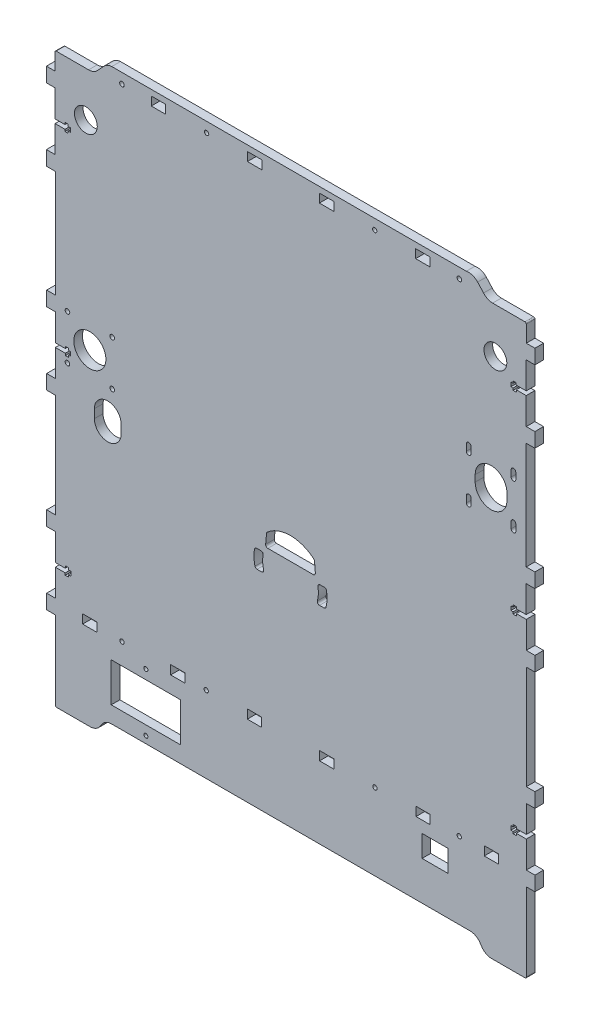
SolidWorks part; units mm, degrees
ref_plane "Спереди" through (0, 0, 0) normal (0, 0, 1) x (1, 0, 0)
ref_plane "Сверху" through (0, 0, 0) normal (0, 1, 0) x (1, 0, 0)
ref_plane "Справа" through (0, 0, 0) normal (1, 0, 0) x (0, 0, -1)
sketch "Эскиз1" plane through (0, 0, 0) normal (0, 0, 1) x (1, 0, 0)
  line L0 (-11.6369, -134.9128) -> (-21.486, -134.9128)
  line L1 (-21.486, -134.9128) -> (-21.486, -128.713)
  line L2 (-11.6369, -128.713) -> (-11.6369, -134.9128)
  line L3 (-21.486, -128.713) -> (-11.6369, -128.713)
  line L4 (-61.6369, -128.7116) -> (-61.6369, -134.9114)
  line L5 (-71.4861, -128.7116) -> (-61.6369, -128.7116)
  line L6 (-71.4861, -134.9114) -> (-71.4861, -128.7116)
  line L7 (-61.6369, -134.9114) -> (-71.4861, -134.9114)
  line L8 (49.4936, -157.9128) -> (49.4936, -142.9128)
  line L9 (49.4936, -142.9128) -> (67.4936, -142.9128)
  line L10 (67.4936, -142.9128) -> (67.4936, -157.9128)
  line L11 (67.4936, -157.9128) -> (49.4936, -157.9128)
  line L12 (-197.4929, 21.4243) -> (-197.4918, 20.0542)
  line L13 (-204.4021, 24.2766) -> (-204.4021, 42.8766)
  line L14 (-195.2929, 25.6494) -> (-195.2929, 25.6766)
  line L15 (127.5652, 42.8766) -> (127.5652, 52.8766)
  line L16 (-193.7921, 24.2485) -> (-193.792, 24.2757)
  line L17 (-195.292, 24.2757) -> (-195.2929, 25.6494)
  line L18 (-195.2921, 21.4269) -> (-195.2921, 21.4541)
  line L19 (-193.7921, 21.4541) -> (-193.7921, 24.2485)
  line L20 (112.4973, 24.3034) -> (112.4973, 24.2763)
  line L21 (114.6973, 24.3037) -> (114.697, 25.6766)
  line L22 (-195.2921, 20.0542) -> (-195.2921, 21.4269)
  line L23 (110.9994, 21.5032) -> (110.9994, 21.4761)
  line L24 (110.9973, 24.2752) -> (110.9994, 21.5032)
  line L25 (121.561, 24.2766) -> (121.561, 42.8766)
  line L26 (-197.4929, 25.6494) -> (-197.4927, 24.2766)
  line L27 (127.6121, -7.1234) -> (127.6121, 2.8766)
  line L28 (112.5004, 20.1034) -> (112.5004, 20.0763)
  line L29 (-204.4053, 21.4566) -> (-204.4053, 21.4766)
  line L30 (121.5652, 52.8766) -> (121.5652, 127.0366)
  line L31 (-210.4021, 42.8766) -> (-210.4021, 52.8766)
  line L32 (-204.4053, 2.8766) -> (-204.4053, 21.4566)
  line L33 (-204.4021, 52.8766) -> (-204.4021, 127.0366)
  line L34 (-114.6824, -134.9128) -> (-124.5316, -134.9128)
  line L35 (-124.5316, -134.9128) -> (-124.5316, -128.713)
  line L36 (-124.5316, -128.713) -> (-114.6824, -128.713)
  line L37 (-114.6824, -128.713) -> (-114.6824, -134.9128)
  line L38 (-175.6509, -134.9128) -> (-185.5001, -134.9128)
  line L39 (-185.5001, -134.9128) -> (-185.5001, -128.713)
  line L40 (-185.5001, -128.713) -> (-175.6509, -128.713)
  line L41 (-175.6509, -128.713) -> (-175.6509, -134.9128)
  line L42 (92.5339, -134.9128) -> (102.3831, -134.9128)
  line L43 (102.3831, -134.9128) -> (102.3831, -128.713)
  line L44 (102.3831, -128.713) -> (92.5339, -128.713)
  line L45 (92.5339, -128.713) -> (92.5339, -134.9128)
  line L46 (55.1377, -134.9128) -> (45.2885, -134.9128)
  line L47 (45.2885, -134.9128) -> (45.2885, -128.713)
  line L48 (45.2885, -128.713) -> (55.1377, -128.713)
  line L49 (55.1377, -128.713) -> (55.1377, -134.9128)
  line L50 (-18.1346, -29.194) -> (-21.1843, -29.194)
  line L51 (-21.5365, -41.694) -> (-18.4403, -41.694)
  line L52 (-64.7445, -41.694) -> (-61.6484, -41.694)
  line L53 (-62.0005, -29.194) -> (-65.0502, -29.194)
  line L54 (-58.1883, -16.8245) -> (-58.7957, -23.7669)
  line L55 (-24.3892, -23.7669) -> (-24.9965, -16.8245)
  line L56 (-57.3014, -25.3976) -> (-25.8835, -25.3976)
  line L57 (-165.6924, -146.4128) -> (-165.6924, -173.4128)
  line L58 (-165.6924, -173.4128) -> (-117.6924, -173.4128)
  line L59 (-117.6924, -173.4128) -> (-117.6924, -146.4128)
  line L60 (-117.6924, -146.4128) -> (-165.6924, -146.4128)
  line L61 (-181.3562, 199.4366) -> (-203.8128, 199.4366)
  line L62 (-170.9916, 206.6945) -> (-175.0871, 202.2149)
  line L63 (127.6153, -128.8434) -> (121.6153, -128.8434)
  line L64 (80.0963, 209.4366) -> (-165.3346, 209.4366)
  line L65 (121.6121, -7.1234) -> (127.6121, -7.1234)
  line L66 (87.9583, 206.8296) -> (92.0585, 202.3542)
  line L67 (98.3301, 199.4366) -> (120.7011, 199.4366)
  line L68 (121.6211, 187.0366) -> (121.6211, 198.5166)
  line L69 (121.5933, 177.0366) -> (127.6211, 177.0366)
  line L70 (127.6211, 177.0366) -> (127.6211, 187.0366)
  line L71 (-204.4021, 42.8766) -> (-210.4021, 42.8766)
  line L72 (120.6695, -193.8634) -> (97.6691, -193.8634)
  line L73 (91.2398, -190.805) -> (89.1831, -187.7854)
  line L74 (-203.4958, -193.8634) -> (-180.3696, -193.8634)
  line L75 (-210.5789, 177.0366) -> (-210.5789, 187.0366)
  line L76 (114.6813, 158.4366) -> (114.6813, 159.8367)
  line L77 (121.7001, -107.4334) -> (114.7001, -107.4334)
  line L78 (-204.6067, 158.4366) -> (-204.6067, 177.0366)
  line L79 (114.7001, -106.0333) -> (112.4992, -106.0333)
  line L80 (-204.4053, -107.4334) -> (-204.4053, -88.8534)
  line L81 (114.7058, -110.2334) -> (121.6153, -110.2334)
  line L82 (121.7001, -107.4334) -> (121.7001, -88.8534)
  line L83 (111.0017, -110.2331) -> (112.5017, -110.2322)
  line L84 (112.4992, -106.0333) -> (112.5001, -107.4331)
  line L85 (111.0001, -107.434) -> (111.0017, -110.2331)
  line L86 (-197.5289, -111.681) -> (-195.3403, -111.6794)
  line L87 (121.5933, 158.4366) -> (114.6813, 158.4366)
  line L88 (114.7057, -111.6332) -> (114.7058, -110.2334)
  line L89 (114.7001, -107.4334) -> (114.7001, -106.0333)
  line L90 (112.5001, -107.4331) -> (111.0001, -107.434)
  line L91 (112.4829, 155.6378) -> (112.4838, 154.2369)
  line L92 (-197.4961, -105.897) -> (-197.4959, -107.4334)
  line L93 (-204.4053, 21.4766) -> (-197.4929, 21.4766)
  line L94 (-197.4929, 21.4766) -> (-197.4929, 21.4243)
  line L95 (-204.5782, 155.6366) -> (-197.6663, 155.6366)
  line L96 (121.6153, -128.8434) -> (121.6153, -110.2334)
  line L97 (121.6097, 2.8766) -> (121.6097, 21.4766)
  line L98 (127.6153, -138.8434) -> (127.6153, -128.8434)
  line L99 (114.7002, 21.4766) -> (121.6097, 21.4766)
  line L100 (-197.6663, 155.6366) -> (-197.6663, 154.2365)
  line L101 (-197.6973, 158.4366) -> (-204.6067, 158.4366)
  line L102 (-195.4973, 158.419) -> (-195.4973, 159.8366)
  line L103 (112.5017, -110.2322) -> (112.5025, -111.6331)
  line L104 (-197.4959, -107.4334) -> (-204.4053, -107.4334)
  line L105 (112.4805, 159.8367) -> (112.4813, 158.4369)
  line L106 (114.6838, 154.2368) -> (114.6838, 155.6366)
  line L107 (-197.5292, -110.2334) -> (-197.5289, -111.681)
  line L108 (110.9813, 158.436) -> (110.9829, 155.6369)
  line L109 (-195.2929, 25.6766) -> (-197.4929, 25.6766)
  line L110 (112.5004, 20.0763) -> (114.7004, 20.0766)
  line L111 (112.4838, 154.2369) -> (114.6838, 154.2368)
  line L112 (110.9829, 155.6369) -> (112.4829, 155.6378)
  line L113 (121.6121, -78.8534) -> (121.6121, -7.1234)
  line L114 (-195.4654, 155.619) -> (-193.9946, 155.619)
  line L115 (112.4962, 25.6762) -> (112.4973, 24.3034)
  line L116 (114.6973, 24.2766) -> (114.6973, 24.3037)
  line L117 (112.4813, 158.4369) -> (110.9813, 158.436)
  line L118 (-195.3352, -105.8955) -> (-197.4961, -105.897)
  line L119 (-193.6832, -110.2778) -> (-193.6885, -107.2844)
  line L120 (-195.3421, -110.2798) -> (-193.6832, -110.2778)
  line L121 (-197.4918, 20.0542) -> (-195.2921, 20.0542)
  line L122 (-195.2921, 21.4541) -> (-193.7921, 21.4541)
  line L123 (114.7004, 20.0766) -> (114.7004, 20.1037)
  line L124 (-204.4416, -110.2334) -> (-197.5292, -110.2334)
  line L125 (-195.3334, -107.2865) -> (-195.3352, -105.8955)
  line L126 (-193.792, 24.2757) -> (-195.292, 24.2757)
  line L127 (-197.6663, 154.2365) -> (-195.4654, 154.2365)
  line L128 (-195.3403, -111.6794) -> (-195.3421, -110.2798)
  line L129 (-197.6973, 159.8366) -> (-197.6973, 158.4366)
  line L130 (-193.6885, -107.2844) -> (-195.3334, -107.2865)
  line L131 (-195.4654, 154.2365) -> (-195.4654, 155.619)
  line L133 (114.6813, 159.8367) -> (112.4805, 159.8367)
  line L134 (-193.9946, 155.619) -> (-193.9946, 158.419)
  line L135 (114.6838, 155.6366) -> (121.5933, 155.6366)
  line L136 (-197.4927, 24.2766) -> (-204.4021, 24.2766)
  line L137 (114.7004, 20.1037) -> (114.7002, 21.4766)
  line L138 (-197.4929, 25.6766) -> (-197.4929, 25.6494)
  line L139 (112.5025, -111.6331) -> (114.7057, -111.6332)
  line L140 (112.4973, 24.2763) -> (110.9973, 24.2752)
  line L141 (-195.4973, 159.8366) -> (-197.6973, 159.8366)
  line L142 (121.5933, 158.4366) -> (121.5933, 177.0366)
  line L143 (114.697, 25.6766) -> (112.4962, 25.6762)
  line L144 (-193.9946, 158.419) -> (-195.4973, 158.419)
  line L145 (-204.4053, -7.1234) -> (-210.4053, -7.1234)
  line L146 (-204.6067, 177.0366) -> (-210.5789, 177.0366)
  line L147 (127.6121, -88.8534) -> (127.6121, -78.8534)
  line L148 (110.9994, 21.4761) -> (112.4994, 21.4772)
  line L149 (121.561, 24.2766) -> (114.6973, 24.2766)
  line L150 (112.4994, 21.4772) -> (112.5004, 20.1034)
  line L151 (-204.4082, -192.8001) -> (-204.4363, -138.8434)
  line L152 (-204.5782, 137.0366) -> (-204.5782, 155.6366)
  line L153 (-210.5782, 127.0366) -> (-210.5782, 137.0366)
  line L154 (-204.4021, 127.0366) -> (-210.5782, 127.0366)
  line L155 (127.5652, 127.0366) -> (127.5652, 137.0366)
  line L156 (127.5652, 137.0366) -> (121.5933, 137.0366)
  line L157 (-137.9789, 205.4366) -> (-127.9789, 205.4366)
  line L158 (-127.9789, 205.4366) -> (-127.9789, 199.4366)
  line L159 (-127.9789, 199.4366) -> (-137.9789, 199.4366)
  line L160 (-137.9789, 199.4366) -> (-137.9789, 205.4366)
  line L161 (55.0211, 199.4366) -> (45.0211, 199.4366)
  line L162 (45.0211, 199.4366) -> (45.0211, 205.4366)
  line L163 (45.0211, 205.4366) -> (55.0211, 205.4366)
  line L164 (55.0211, 205.4366) -> (55.0211, 199.4366)
  line L165 (-61.3789, 199.4366) -> (-71.3789, 199.4366)
  line L166 (-71.3789, 199.4366) -> (-71.3789, 205.4366)
  line L167 (-71.3789, 205.4366) -> (-61.3789, 205.4366)
  line L169 (-11.5789, 199.4366) -> (-21.5789, 199.4366)
  line L170 (-21.5789, 199.4366) -> (-21.5789, 205.4366)
  line L171 (-21.5789, 205.4366) -> (-11.5789, 205.4366)
  line L173 (127.6211, 187.0366) -> (121.6211, 187.0366)
  line L174 (121.5933, 137.0366) -> (121.5933, 155.6366)
  line L175 (121.5652, 127.0366) -> (127.5652, 127.0366)
  line L176 (-210.4053, 2.8766) -> (-204.4053, 2.8766)
  line L177 (-204.4416, -128.8434) -> (-204.4416, -110.2334)
  line L178 (-204.4053, -78.8534) -> (-204.4053, -7.1234)
  line L179 (-210.4363, -128.8434) -> (-204.4416, -128.8434)
  line L180 (-210.4053, -88.8534) -> (-210.4053, -78.8534)
  line L181 (-210.4053, -7.1234) -> (-210.4053, 2.8766)
  line L182 (-210.4053, -78.8534) -> (-204.4053, -78.8534)
  line L183 (-173.8615, -190.8095) -> (-171.8064, -187.7888)
  line L184 (127.5652, 52.8766) -> (121.5652, 52.8766)
  line L185 (121.7918, -192.6916) -> (121.7918, -138.8434)
  line L186 (-165.2966, -184.7491) -> (82.6717, -184.7491)
  line L187 (-210.4363, -138.8434) -> (-210.4363, -128.8434)
  line L188 (-204.4363, -138.8434) -> (-210.4363, -138.8434)
  line L189 (-210.5782, 137.0366) -> (-204.5782, 137.0366)
  line L190 (-210.5789, 187.0366) -> (-204.5789, 187.0366)
  line L191 (-210.4021, 52.8766) -> (-204.4021, 52.8766)
  line L192 (-204.4053, -88.8534) -> (-210.4053, -88.8534)
  line L193 (121.7918, -138.8434) -> (127.6153, -138.8434)
  line L194 (127.6121, -78.8534) -> (121.6121, -78.8534)
  line L195 (127.6121, 2.8766) -> (121.6097, 2.8766)
  line L196 (-204.5789, 187.0366) -> (-204.5789, 198.2588)
  line L197 (121.561, 42.8766) -> (127.5652, 42.8766)
  line L198 (121.7001, -88.8534) -> (127.6121, -88.8534)
  line L199 (-158.8564, -7.694) -> (-158.8564, -1.694)
  line L200 (86.2572, 90.556) -> (86.2572, 86.056)
  line L201 (111.1572, 75.056) -> (111.1572, 70.556)
  line L202 (108.2572, 86.056) -> (108.2572, 90.556)
  line L203 (114.3572, 101.556) -> (114.3572, 106.056)
  line L204 (111.1572, 106.056) -> (111.1572, 101.556)
  line L205 (114.3572, 70.556) -> (114.3572, 75.056)
  line L206 (80.1572, 75.056) -> (80.1572, 70.556)
  line L207 (83.3572, 70.556) -> (83.3572, 75.056)
  line L208 (83.3572, 101.556) -> (83.3572, 106.056)
  line L209 (-177.3564, -1.694) -> (-177.3564, -7.694)
  line L210 (80.1572, 106.056) -> (80.1572, 101.556)
  line L211 (-61.3789, 205.4366) -> (-61.3789, 199.4366)
  line L212 (-11.5789, 199.4366) -> (-11.5789, 205.4366)
  line L213 (-141.6924, -189.1404) -> (-141.6924, -133.1187) construction
  arc A0 (80.1572, 70.556) -> (83.3572, 70.556) centre (81.7572, 70.556) ccw
  arc A1 (80.1572, 101.556) -> (83.3572, 101.556) centre (81.7572, 101.556) ccw
  circle A2 centre (-183.2567, 168.4366) radius 7.9
  circle A3 centre (100.2433, 168.4366) radius 7.9
  arc A4 (-16.6559, -30.4419) -> (-18.1346, -29.194) centre (-18.1346, -30.694) ccw
  arc A5 (-21.1843, -29.194) -> (-22.6563, -30.9825) centre (-21.1843, -30.694) ccw
  arc A6 (-22.9831, -39.7973) -> (-22.6563, -30.9825) centre (-41.5924, -34.694) ccw
  arc A7 (-22.9831, -39.7973) -> (-21.5365, -41.694) centre (-21.5365, -40.194) ccw
  arc A8 (-65.0502, -29.194) -> (-66.5289, -30.4419) centre (-65.0502, -30.694) ccw
  arc A9 (-66.5289, -30.4419) -> (-66.2039, -40.5407) centre (-41.5924, -34.694) ccw
  arc A10 (-66.2039, -40.5407) -> (-64.7445, -41.694) centre (-64.7445, -40.194) ccw
  arc A11 (-61.6484, -41.694) -> (-60.2018, -39.7973) centre (-61.6484, -40.194) ccw
  arc A12 (-60.5285, -30.9825) -> (-60.2018, -39.7973) centre (-41.5924, -34.694) ccw
  arc A13 (-60.5285, -30.9825) -> (-62.0005, -29.194) centre (-62.0005, -30.694) ccw
  arc A14 (-16.9809, -40.5407) -> (-16.6559, -30.4419) centre (-41.5924, -34.694) ccw
  arc A15 (-18.4403, -41.694) -> (-16.9809, -40.5407) centre (-18.4403, -40.194) ccw
  arc A16 (-57.6664, -15.8131) -> (-58.1883, -16.8245) centre (-56.694, -16.9552) ccw
  arc A17 (-25.5185, -15.8131) -> (-57.6664, -15.8131) centre (-41.5924, -34.694) ccw
  arc A18 (-24.9965, -16.8245) -> (-25.5185, -15.8131) centre (-26.4908, -16.9552) ccw
  arc A19 (-25.8835, -25.3976) -> (-24.3892, -23.7669) centre (-25.8835, -23.8976) ccw
  arc A20 (-58.7957, -23.7669) -> (-57.3014, -25.3976) centre (-57.3014, -23.8976) ccw
  circle A21 centre (-158.2789, 202.4366) radius 1.6
  arc A22 (-203.8128, 199.4366) -> (-204.5789, 198.2588) centre (-203.7028, 198.5271) ccw
  arc A23 (-181.3562, 199.4366) -> (-175.0871, 202.2149) centre (-181.3746, 207.9403) ccw
  arc A24 (-165.3346, 209.4366) -> (-170.9916, 206.6945) centre (-164.7183, 200.959) ccw
  circle A25 centre (75.3211, 202.4366) radius 1.6
  arc A26 (87.9583, 206.8296) -> (80.0963, 209.4366) centre (81.6909, 201.0876) ccw
  arc A27 (-180.3696, -193.8634) -> (-173.8615, -190.8095) centre (-180.3894, -185.3595) ccw
  arc A28 (120.6695, -193.8634) -> (121.7918, -192.6916) centre (120.6892, -192.7589) ccw
  arc A29 (-165.2966, -184.7491) -> (-171.8064, -187.7888) centre (-165.2921, -193.2491) ccw
  arc A30 (-204.4082, -192.8001) -> (-203.4958, -193.8634) centre (-203.4564, -192.9065) ccw
  arc A31 (89.1831, -187.7854) -> (82.6717, -184.7491) centre (82.6717, -193.2491) ccw
  arc A32 (91.2398, -190.805) -> (97.6691, -193.8634) centre (97.7466, -185.4133) ccw
  arc A34 (92.0585, 202.3542) -> (98.3301, 199.4366) centre (98.4899, 207.9796) ccw
  circle A35 centre (16.7211, 202.4366) radius 1.5
  circle A36 centre (-99.6789, 202.4366) radius 1.5
  circle A37 centre (-196.0064, 47.306) radius 1.6
  arc A38 (-177.3564, -7.694) -> (-158.8564, -7.694) centre (-168.1064, -7.694) ccw
  circle A39 centre (-165.0064, 16.306) radius 1.6
  circle A40 centre (-196.0064, 16.306) radius 1.6
  arc A41 (86.2572, 86.056) -> (108.2572, 86.056) centre (97.2572, 86.056) ccw
  arc A42 (108.2572, 90.556) -> (86.2572, 90.556) centre (97.2572, 90.556) ccw
  arc A43 (114.3572, 75.056) -> (111.1572, 75.056) centre (112.7572, 75.056) ccw
  circle A44 centre (-180.5064, 31.806) radius 11.1
  circle A45 centre (-165.0064, 47.306) radius 1.6
  arc A46 (114.3572, 106.056) -> (111.1572, 106.056) centre (112.7572, 106.056) ccw
  arc A47 (111.1572, 101.556) -> (114.3572, 101.556) centre (112.7572, 101.556) ccw
  arc A48 (111.1572, 70.556) -> (114.3572, 70.556) centre (112.7572, 70.556) ccw
  arc A49 (83.3572, 75.056) -> (80.1572, 75.056) centre (81.7572, 75.056) ccw
  arc A50 (-158.8564, -1.694) -> (-177.3564, -1.694) centre (-168.1064, -1.694) ccw
  arc A51 (83.3572, 106.056) -> (80.1572, 106.056) centre (81.7572, 106.056) ccw
  circle A52 centre (75.2316, -131.7306) radius 1.5
  circle A53 centre (16.8441, -131.6894) radius 1.5
  circle A54 centre (-99.9433, -131.7314) radius 1.5
  circle A55 centre (-158.2786, -131.7671) radius 1.5
  arc A57 (121.6211, 198.5166) -> (120.7011, 199.4366) centre (120.7011, 198.5166) ccw
  circle A58 centre (-141.6924, -179.9491) radius 1.4
  circle A59 centre (-141.6924, -139.9491) radius 1.4
  point P319 (-207.5789, 187.0366)
  point P320 (124.6211, 187.0366)
  point P322 (-11.5789, 202.4366)
  point P326 (-61.3789, 202.4366)
  dimension "D1" = 15.8
  dimension "D2" = 15.8
  dimension "D3" = 22.2
  dimension "D6" = 283.5
  dimension "D35" = 6
  dimension "D38" = 0.92
  dimension "D43" = 46.3
  dimension "D96" = 2.8
  dimension "D97" = 2.8
  dimension "D4" = 403.3
  dimension "D5" = 403.3
  dimension "D7" = 6
  dimension "D8" = 338.2
  dimension "D9" = 10
  dimension "D10" = 12.4
  dimension "D11" = 10
  dimension "D12" = 46.3
  dimension "D13" = 6
  dimension "D14" = 66.6
  dimension "D15" = 4
  dimension "D16" = 7
  dimension "D17" = 7
  dimension "D18" = 4
  dimension "D19" = 4
  dimension "D20" = 7
  dimension "D21" = 7
  dimension "D22" = 4
  dimension "D23" = 6
  dimension "D24" = 28.3
  dimension "D25" = 28.3
  dimension "D26" = 28.3
  dimension "D27" = 10
  dimension "D28" = 10
  dimension "D29" = 10
  dimension "D30" = 10
  dimension "D31" = 10
  dimension "D32" = 12.4
  dimension "D33" = 21.35
  dimension "D34" = 21.35
  dimension "D36" = 6
  dimension "D37" = 6
  dimension "D39" = 28.3
  dimension "D40" = 66.6
  dimension "D41" = 31
  dimension "D42" = 31
  dimension "D44" = 39.8
  dimension "D45" = 18.6
  dimension "D46" = 326.2
  dimension "D47" = 2.8
  dimension "D48" = 18.6
  dimension "D49" = 6
  dimension "D50" = 10
  dimension "D51" = 74.16
  dimension "D52" = 6
  dimension "D53" = 10
  dimension "D54" = 18.6
  dimension "D55" = 2.8
  dimension "D56" = 18.6
  dimension "D57" = 31
  dimension "D58" = 31
  dimension "D59" = 6
  dimension "D60" = 10
  dimension "D61" = 71.73
  dimension "D62" = 10
  dimension "D63" = 6
  dimension "D64" = 18.58
  dimension "D65" = 2.8
  dimension "D66" = 18.61
  dimension "D67" = 6
  dimension "D68" = 10
  dimension "D69" = 166.56
  dimension "D70" = 131.73
  dimension "D71" = 55.02
  dimension "D72" = 18.6
  dimension "D73" = 18.6
  dimension "D74" = 2.8
  dimension "D75" = 10
  dimension "D76" = 10
  dimension "D77" = 74.16
  dimension "D78" = 10
  dimension "D79" = 18.6
  dimension "D80" = 2.8
  dimension "D81" = 18.6
  dimension "D82" = 10
  dimension "D83" = 71.73
  dimension "D84" = 10
  dimension "D85" = 6
  dimension "D86" = 6
  dimension "D87" = 6
  dimension "D88" = 6
  dimension "D89" = 18.58
  dimension "D90" = 2.8
  dimension "D91" = 18.61
  dimension "D92" = 10
  dimension "D93" = 6
  dimension "D94" = 166.56
  dimension "D95" = 55.02
  dimension "D98" = 4.8
  dimension "D99" = 44.8
extrude "Бобышка-Вытянуть1" add sketch "Эскиз1" along normal blind 6
